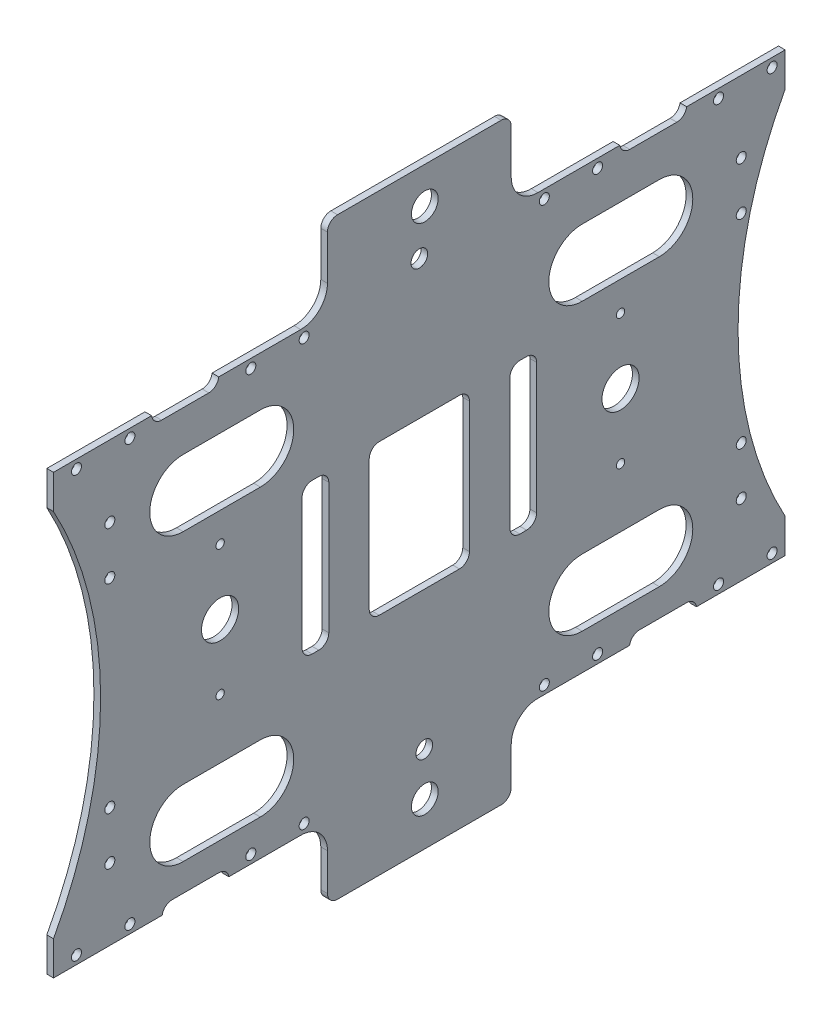
SolidWorks part; units mm, degrees
ref_plane "前视基准面" through (0, 0, 0) normal (0, 0, 1) x (1, 0, 0)
ref_plane "上视基准面" through (0, 0, 0) normal (0, 1, 0) x (1, 0, 0)
ref_plane "右视基准面" through (0, 0, 0) normal (1, 0, 0) x (0, 0, -1)
sketch "Sketch1" plane through (0, 0, 0) normal (1, 0, 0) x (0, 0, -1)
  line L0 (34.8552, 137.2723) -> (34.8552, 77.1155) construction
  line L1 (-184.1448, 87.2892) -> (34.8552, 87.2892)
  line L2 (-184.1448, 87.2892) -> (-184.1448, -43.8053)
  line L3 (-184.1448, -43.8053) -> (34.8552, -43.8053)
  line L4 (34.8552, 87.2892) -> (34.8552, -43.8053)
  line L5 (-184.1448, 87.2892) -> (34.8552, -43.8053) construction
  line L6 (-184.1448, -43.8053) -> (34.8552, 87.2892) construction
  line L7 (-184.1448, 137.2723) -> (-184.1448, 77.1155) construction
  line L8 (-184.1448, -93.7795) -> (-184.1448, -33.6227) construction
  point P0 (-74.6448, 21.742)
extrude "Boss-Extrude1" add sketch "Sketch1" along normal blind 2
sketch "Sketch2" plane through (2, 0, 0) normal (1, 0, 0) x (0, 0, -1)
  line L0 (-167.1842, 84.6899) -> (-189.8208, 84.6899) construction
  line L1 (-87.1347, 86.162) -> (-87.1347, 101.7527) construction
  line L2 (-180.2416, -41.2557) -> (-183.5915, -41.2557) construction
  line L3 (-182.1347, 21.162) -> (-173.3707, 21.162) construction
  circle A0 centre (-177.2782, 84.6899) radius 1.5
  circle A1 centre (-161.2773, 84.6899) radius 1.5
  circle A2 centre (14.9073, 84.6899) radius 1.5
  circle A3 centre (30.9402, 84.6899) radius 1.5
  circle A4 centre (-125.0909, 84.6899) radius 1.5
  circle A5 centre (-109.1212, 84.6899) radius 1.5
  circle A6 centre (-37.2397, 84.6899) radius 1.5
  circle A7 centre (-21.2903, 84.6899) radius 1.5
  circle A8 centre (-177.2782, -41.2557) radius 1.5
  circle A9 centre (-161.2773, -41.2557) radius 1.5
  circle A10 centre (-125.0909, -41.2557) radius 1.5
  circle A11 centre (-109.1212, -41.2557) radius 1.5
  circle A12 centre (-21.2903, -41.2557) radius 1.5
  circle A13 centre (-37.2397, -41.2557) radius 1.5
  circle A14 centre (14.9073, -41.2557) radius 1.5
  circle A15 centre (30.9402, -41.2557) radius 1.5
extrude "Cut-Extrude1" cut sketch "Sketch2" against normal blind 2
sketch "Sketch3" plane through (2, 0, 0) normal (1, 0, 0) x (0, 0, -1)
  line L0 (34.8552, 87.2892) -> (-184.1448, 87.2892) construction
  line L1 (-154.7837, 89.9448) -> (-134.683, 89.9448)
  line L2 (-154.7837, 89.9448) -> (-154.7837, 84.6337)
  line L3 (-154.7837, 84.6337) -> (-134.683, 84.6337)
  line L4 (-134.683, 89.9448) -> (-134.683, 84.6337)
  line L5 (-154.7837, 89.9448) -> (-134.683, 84.6337) construction
  line L6 (-154.7837, 84.6337) -> (-134.683, 89.9448) construction
  line L7 (-184.1448, -43.8053) -> (34.8552, -43.8053) construction
  line L8 (-14.6371, 89.8214) -> (5.3843, 89.8214)
  line L9 (-14.6371, 89.8214) -> (-14.6371, 84.7571)
  line L10 (-14.6371, 84.7571) -> (5.3843, 84.7571)
  line L11 (5.3843, 89.8214) -> (5.3843, 84.7571)
  line L12 (-14.6371, 89.8214) -> (5.3843, 84.7571) construction
  line L13 (-14.6371, 84.7571) -> (5.3843, 89.8214) construction
  line L14 (-151.6036, -41.2639) -> (-131.6627, -41.2639)
  line L15 (-151.6036, -41.2639) -> (-151.6036, -46.3467)
  line L16 (-151.6036, -46.3467) -> (-131.6627, -46.3467)
  line L17 (-131.6627, -41.2639) -> (-131.6627, -46.3467)
  line L18 (-151.6036, -41.2639) -> (-131.6627, -46.3467) construction
  line L19 (-151.6036, -46.3467) -> (-131.6627, -41.2639) construction
  line L21 (-11.6994, -41.2643) -> (8.3072, -41.2643)
  line L22 (-11.6994, -41.2643) -> (-11.6994, -46.3463)
  line L23 (-11.6994, -46.3463) -> (8.3072, -46.3463)
  line L24 (8.3072, -41.2643) -> (8.3072, -46.3463)
  line L25 (-11.6994, -41.2643) -> (8.3072, -46.3463) construction
  line L26 (-11.6994, -46.3463) -> (8.3072, -41.2643) construction
  point P0 (-144.7333, 87.2892)
  point P7 (-4.6264, 87.2892)
  point P12 (-141.6332, -43.8053)
  point P19 (-1.6961, -43.8053)
extrude "Cut-Extrude2" cut sketch "Sketch3" against normal blind 2
fillet "Fillet1" radius 3 8 edges at (1, 84.6337, 154.7837) (1, 84.6337, 134.683) (1, 84.7571, -5.3843) (1, 84.7571, 14.6371) (1, -41.2643, 11.6994) (1, -41.2643, -8.3072) (1, -41.2639, 131.6627) (1, -41.2639, 151.6036)
sketch "Sketch4" plane through (2, 0, 0) normal (1, 0, 0) x (0, 0, -1)
  line L2 (-182.6622, 21.742) -> (-175.2516, 21.742) construction
  line L5 (21.7084, -22.3962) -> (-167.297, -22.3962) construction
  line L6 (21.7084, -22.3962) -> (21.7084, 65.8802) construction
  line L7 (21.7084, 65.8802) -> (-167.297, 65.8802) construction
  line L8 (-167.297, -22.3962) -> (-167.297, 65.8802) construction
  line L9 (21.7084, -22.3962) -> (-167.297, 65.8802) construction
  line L10 (21.7084, 65.8802) -> (-167.297, -22.3962) construction
  line L11 (21.7084, -8.0311) -> (-167.297, -8.0311) construction
  line L12 (21.7084, -8.0311) -> (21.7084, 51.515) construction
  line L13 (21.7084, 51.515) -> (-167.297, 51.515) construction
  line L14 (-167.297, -8.0311) -> (-167.297, 51.515) construction
  line L15 (21.7084, -8.0311) -> (-167.297, 51.515) construction
  line L16 (21.7084, 51.515) -> (-167.297, -8.0311) construction
  circle A0 centre (-167.297, 65.8802) radius 1.5
  circle A1 centre (-167.297, 51.515) radius 1.5
  circle A2 centre (-167.297, -8.0311) radius 1.5
  circle A3 centre (-167.297, -22.3962) radius 1.5
  circle A4 centre (21.7084, 65.8802) radius 1.5
  circle A5 centre (21.7084, 51.515) radius 1.5
  circle A6 centre (21.7084, -8.0311) radius 1.5
  circle A7 centre (21.7084, -22.3962) radius 1.5
  point P2 (-72.7943, 21.742)
  point P9 (-72.7943, 21.742)
extrude "Cut-Extrude3" cut sketch "Sketch4" against normal blind 2
sketch "Sketch5" plane through (2, 0, 0) normal (1, 0, 0) x (0, 0, -1)
  line L0 (-74.6448, 87.2892) -> (-74.6448, 52.4969) construction
  line L1 (-184.1448, 77.1155) -> (-184.1448, -33.6227)
  line L2 (-72.2955, 23.9806) -> (-92.6605, 23.9806) construction
  line L3 (-18.6199, 43.6427) -> (-10.2117, 43.6427) construction
  line L4 (-18.6199, 43.6427) -> (-18.6199, 4.6427) construction
  line L9 (-18.6199, 4.6427) -> (-10.2117, 4.6427) construction
  line L10 (-10.2117, 43.6427) -> (-10.2117, 4.6427) construction
  line L15 (-18.6199, 43.6427) -> (-10.2117, 4.6427) construction
  line L16 (-78.5893, 42.2766) -> (-70.7003, 42.2766) construction
  line L21 (-78.5893, 42.2766) -> (-78.5893, 5.6846) construction
  line L22 (-78.5893, 5.6846) -> (-70.7003, 5.6846) construction
  line L27 (-70.7003, 42.2766) -> (-70.7003, 5.6846) construction
  line L28 (-78.5893, 42.2766) -> (-70.7003, 5.6846) construction
  line L33 (-78.5893, 5.6846) -> (-70.7003, 42.2766) construction
  line L34 (-18.6199, 4.6427) -> (-10.2117, 43.6427) construction
  line L43 (-138.4847, 43.747) -> (-130.0766, 43.747) construction
  line L46 (34.8552, 77.1155) -> (34.8552, -33.6227)
  line L49 (-138.4847, 43.747) -> (-138.4847, 4.747) construction
  line L52 (-25.8971, 62.4969) -> (-2.7991, 62.4969) construction
  line L53 (-25.8971, 72.4969) -> (-2.7991, 72.4969)
  line L54 (-25.8971, 52.4969) -> (-2.7991, 52.4969)
  line L55 (-25.8971, -23.0278) -> (-2.7991, -23.0278) construction
  line L56 (-25.8971, -33.0278) -> (-2.7991, -33.0278)
  line L57 (-25.8971, -13.0278) -> (-2.7991, -13.0278)
  line L58 (-138.4847, 4.747) -> (-130.0766, 4.747) construction
  line L69 (-130.0766, 43.747) -> (-130.0766, 4.747) construction
  line L72 (-122.2378, 62.4969) -> (-145.3359, 62.4969) construction
  line L73 (-122.2378, 72.4969) -> (-145.3359, 72.4969)
  line L74 (-122.2378, 52.4969) -> (-145.3359, 52.4969)
  line L75 (-122.2378, -23.0278) -> (-145.3359, -23.0278) construction
  line L76 (-122.2378, -33.0278) -> (-145.3359, -33.0278)
  line L77 (-122.2378, -13.0278) -> (-145.3359, -13.0278)
  line L78 (-138.4847, 43.747) -> (-130.0766, 4.747) construction
  line L79 (-138.4847, 4.747) -> (-130.0766, 43.747) construction
  line L80 (34.8552, -43.8053) -> (34.8552, 87.2892) construction
  line L81 (-105.7471, 16.6727) -> (-43.5425, 16.6727) construction
  line L82 (-105.7471, 16.6727) -> (-105.7471, 31.2885) construction
  line L83 (-105.7471, 31.2885) -> (-43.5425, 31.2885) construction
  line L84 (-43.5425, 16.6727) -> (-43.5425, 31.2885) construction
  line L85 (-105.7471, 16.6727) -> (-43.5425, 31.2885) construction
  line L86 (-105.7471, 31.2885) -> (-43.5425, 16.6727) construction
  line L87 (-109.7471, 46.4806) -> (-101.7471, 46.4806)
  line L88 (-109.7471, 46.4806) -> (-109.7471, 1.4806)
  line L89 (-109.7471, 1.4806) -> (-101.7471, 1.4806)
  line L90 (-101.7471, 46.4806) -> (-101.7471, 1.4806)
  line L91 (-109.7471, 46.4806) -> (-101.7471, 1.4806) construction
  line L92 (-109.7471, 1.4806) -> (-101.7471, 46.4806) construction
  line L93 (-39.5425, 46.4806) -> (-47.5425, 46.4806)
  line L94 (-39.5425, 46.4806) -> (-39.5425, 1.4806)
  line L95 (-39.5425, 1.4806) -> (-47.5425, 1.4806)
  line L96 (-47.5425, 46.4806) -> (-47.5425, 1.4806)
  line L97 (-39.5425, 46.4806) -> (-47.5425, 1.4806) construction
  line L98 (-39.5425, 1.4806) -> (-47.5425, 46.4806) construction
  arc A10 (-25.8971, 72.4969) -> (-25.8971, 52.4969) centre (-25.8971, 62.4969) ccw
  arc A11 (-2.7991, 52.4969) -> (-2.7991, 72.4969) centre (-2.7991, 62.4969) ccw
  arc A12 (-25.8971, -33.0278) -> (-25.8971, -13.0278) centre (-25.8971, -23.0278) cw
  arc A13 (-2.7991, -13.0278) -> (-2.7991, -33.0278) centre (-2.7991, -23.0278) cw
  arc A27 (-122.2378, 72.4969) -> (-122.2378, 52.4969) centre (-122.2378, 62.4969) cw
  arc A28 (-145.3359, 52.4969) -> (-145.3359, 72.4969) centre (-145.3359, 62.4969) cw
  arc A29 (-122.2378, -33.0278) -> (-122.2378, -13.0278) centre (-122.2378, -23.0278) ccw
  arc A30 (-145.3359, -13.0278) -> (-145.3359, -33.0278) centre (-145.3359, -23.0278) ccw
  circle A40 centre (-74.6448, 42.2766) radius 1.25
  circle A41 centre (-74.6448, 5.6846) radius 1.25
  circle A46 centre (-74.6448, 23.9806) radius 5.5651
  arc A47 (-184.1448, 77.1155) -> (-184.1448, -33.6227) centre (-285.8106, 21.7464) cw
  arc A48 (34.8552, 77.1155) -> (34.8552, -33.6227) centre (136.521, 21.7464) ccw
  circle A49 centre (-14.4158, 43.6427) radius 1.25
  circle A50 centre (-14.4158, 4.6427) radius 1.25
  circle A51 centre (-14.4158, 24.1427) radius 5.5651
  circle A52 centre (-134.2807, 43.747) radius 1.25
  circle A53 centre (-134.2807, 4.747) radius 1.25
  circle A54 centre (-134.2807, 24.247) radius 5.5651
  point P5 (-74.6448, 23.9806)
  point P9 (-14.4158, 24.1427)
  point P10 (-14.4158, 24.1427)
  point P11 (-74.6448, 23.9806)
  point P16 (-74.6448, 23.9806)
  point P17 (-74.6448, 23.9806)
  point P28 (-14.4158, 24.1427)
  point P29 (-14.4158, 24.1427)
  point P38 (-134.2807, 24.247)
  point P39 (-134.2807, 24.247)
  point P44 (-134.2807, 24.247)
  point P45 (-134.2807, 24.247)
  point P56 (-105.7471, 23.9806)
  point P61 (-43.5425, 23.9806)
  point P64 (-14.3481, 62.4969)
  point P71 (-14.3481, -23.0278)
  point P112 (-133.7868, 62.4969)
  point P119 (-133.7868, -23.0278)
  dimension "D5" = 0
  dimension "D1" = 45
  dimension "D2" = 45
  dimension "D3" = 8
  dimension "D4" = 8
extrude "Cut-Extrude4" cut sketch "Sketch5" against normal blind 10
sketch "Sketch6" plane through (2, 0, 0) normal (1, 0, 0) x (0, 0, -1)
  line L0 (-182.6622, 22.8188) -> (-173.3682, 22.8188) construction
  line L1 (-47.1448, 77.1155) -> (-47.1448, 108.8978) construction
  line L3 (-102.1448, 111.5484) -> (-47.1448, 111.5484)
  line L4 (-102.1448, 111.5484) -> (-102.1448, 57.0915)
  line L5 (-102.1448, 57.0915) -> (-47.1448, 57.0915)
  line L6 (-47.1448, 111.5484) -> (-47.1448, 57.0915)
  line L11 (-47.1448, -65.9107) -> (-47.1448, -11.4538)
  line L12 (-102.1448, -11.4538) -> (-47.1448, -11.4538)
  line L13 (-102.1448, -65.9107) -> (-102.1448, -11.4538)
  line L14 (-102.1448, -65.9107) -> (-47.1448, -65.9107)
  line L16 (-14.6371, 87.2892) -> (-134.683, 87.2892) construction
  line L17 (-102.1448, 77.1155) -> (-102.1448, 108.6937) construction
  point P1 (-74.66, 87.2892)
extrude "Boss-Extrude2" add sketch "Sketch6" against normal up to surface (2 mm away) up to face at (0, 24.247, 128.7155)
fillet "Fillet2" radius 8 4 edges at (1, 87.2892, 102.1448) (1, 87.2892, 47.1448) (1, -43.8053, 47.1448) (1, -43.8053, 102.1448)
fillet "Fillet3" radius 3 4 edges at (1, 111.5484, 102.1448) (1, 111.5484, 47.1448) (1, -65.9107, 102.1448) (1, -65.9107, 47.1448)
sketch "Sketch7" plane through (2, 0, 0) normal (1, 0, 0) x (0, 0, -1)
  line L0 (-73.0166, 108.9662) -> (-73.0166, 124.2819) construction
  circle A0 centre (-73.0166, 100.6646) radius 4
  circle A1 centre (-73.0166, -52.9913) radius 4
extrude "Cut-Extrude5" cut sketch "Sketch7" against normal blind 10
sketch "Sketch8" plane through (2, 0, 0) normal (1, 0, 0) x (0, 0, -1)
  line L0 (-73.1622, 29.5457) -> (-73.1622, 23.9806) construction
  line L2 (-77.1448, 87.9806) -> (-72.1448, 87.9806) construction
  line L3 (-77.1448, 87.9806) -> (-77.1448, -40.0194) construction
  line L4 (-77.1448, -40.0194) -> (-72.1448, -40.0194) construction
  line L5 (-72.1448, 87.9806) -> (-72.1448, -40.0194) construction
  line L6 (-77.1448, 87.9806) -> (-72.1448, -40.0194) construction
  line L7 (-77.1448, -40.0194) -> (-72.1448, 87.9806) construction
  line L8 (-86.6448, 46.4806) -> (-62.6448, 46.4806)
  line L9 (-89.6448, 43.4806) -> (-89.6448, 4.4806)
  line L10 (-86.6448, 1.4806) -> (-62.6448, 1.4806)
  line L11 (-59.6448, 43.4806) -> (-59.6448, 4.4806)
  line L12 (-89.6448, 46.4806) -> (-59.6448, 1.4806) construction
  line L13 (-89.6448, 1.4806) -> (-59.6448, 46.4806) construction
  circle A1 centre (-74.6448, 87.9806) radius 2.5
  circle A2 centre (-73.1622, -40.0194) radius 2.5
  arc A3 (-89.6448, 4.4806) -> (-86.6448, 1.4806) centre (-86.6448, 4.4806) ccw
  arc A4 (-62.6448, 1.4806) -> (-59.6448, 4.4806) centre (-62.6448, 4.4806) ccw
  arc A5 (-62.6448, 46.4806) -> (-59.6448, 43.4806) centre (-62.6448, 43.4806) cw
  arc A6 (-86.6448, 46.4806) -> (-89.6448, 43.4806) centre (-86.6448, 43.4806) ccw
  point P1 (-74.6448, 23.9806)
  point P13 (-74.6448, 23.9806)
  dimension "D2" = 30
  dimension "D4" = 3
  dimension "D1" = 128
  dimension "D3" = 45
extrude "Cut-Extrude6" cut sketch "Sketch8" against normal blind 3
fillet "Fillet4" radius 3 8 edges at (1, 46.4806, 47.5425) (1, 46.4806, 39.5425) (1, 1.4806, 47.5425) (1, 1.4806, 39.5425) (1, 1.4806, 101.7471) (1, 1.4806, 109.7471) (1, 46.4806, 101.7471) (1, 46.4806, 109.7471)
